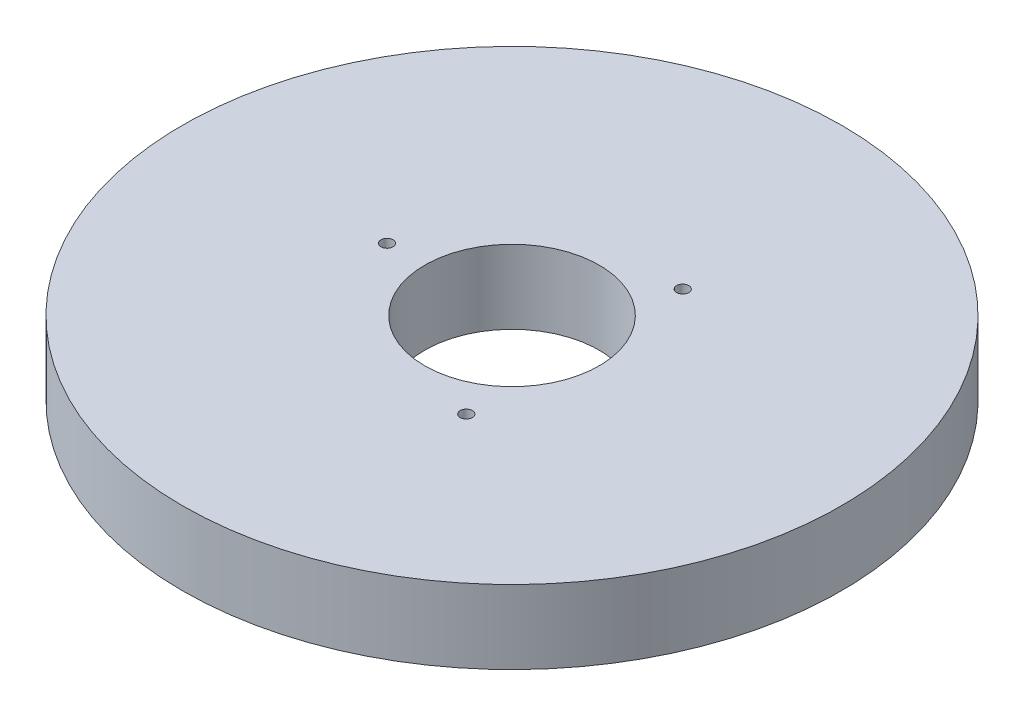
SolidWorks part; units mm, degrees
ref_plane "Front Plane" through (0, 0, 0) normal (0, 0, 1) x (1, 0, 0)
ref_plane "Top Plane" through (0, 0, 0) normal (0, 1, 0) x (1, 0, 0)
ref_plane "Right Plane" through (0, 0, 0) normal (1, 0, 0) x (0, 0, -1)
sketch "Sketch1" plane through (0, 0, 0) normal (0, 1, 0) x (1, 0, 0)
  circle A0 centre (0, 0) radius 85
  dimension "FLANGE_OD" = 170
extrude "Boss-Extrude1" add sketch "Sketch1" along normal blind 19
sketch "Sketch2" plane through (0, 0, 0) normal (0, 1, 0) x (1, 0, 0)
  circle A0 centre (0, 0) radius 22.5
  dimension "BORE_D" = 45
extrude "Cut-Extrude1" cut sketch "Sketch2" along normal through all
sketch "Sketch3" plane through (0, 19, 0) normal (0, 1, 0) x (1, 0, 0)
  circle A0 centre (0, 0) radius 32.2354 construction
  circle A1 centre (-32.2354, 0) radius 1.5673
  dimension "BOLT_D" = 3.1347
  dimension "BOLT_PCD" = 64.4708
extrude "Cut-Extrude2" cut sketch "Sketch3" against normal blind 13.7727
pattern_circular "CirPattern1" count 3 over 360 about axis through (0, 0, 0) along (0, 1, 0) of "Cut-Extrude2"
